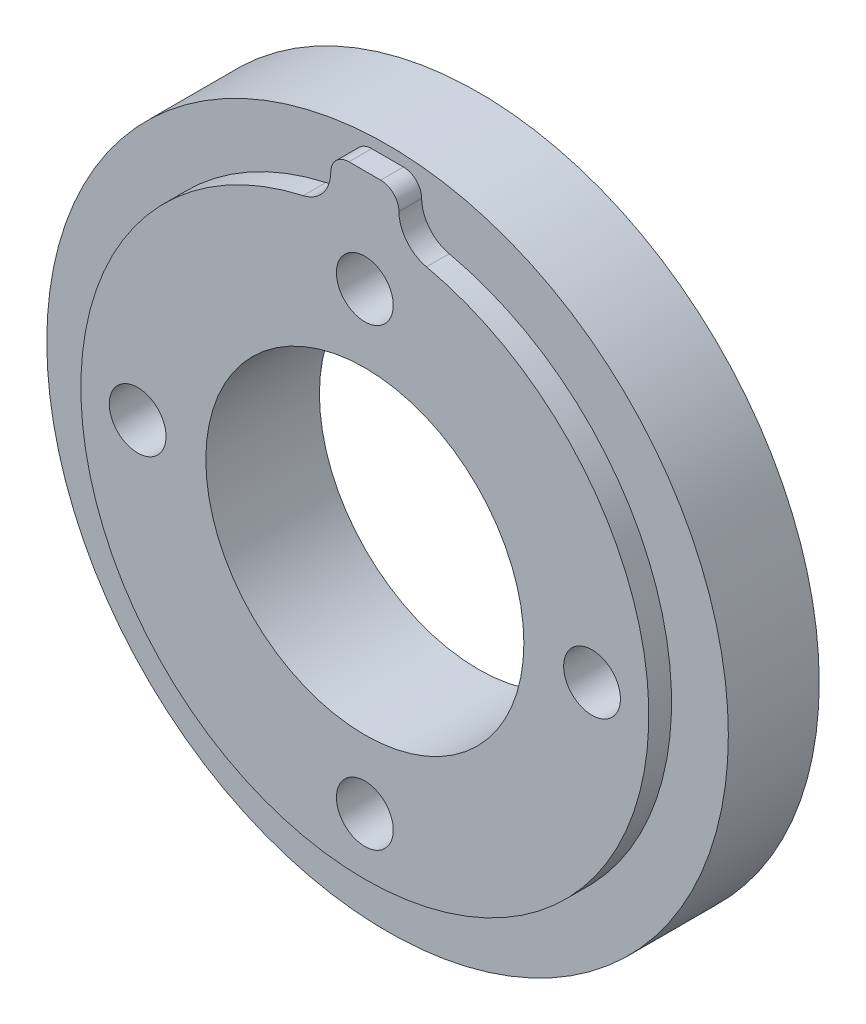
SolidWorks part; units mm, degrees
ref_plane "正面" through (0, 0, 0) normal (0, 0, 1) x (1, 0, 0)
ref_plane "平面" through (0, 0, 0) normal (0, 1, 0) x (1, 0, 0)
ref_plane "右側面" through (0, 0, 0) normal (1, 0, 0) x (0, 0, -1)
sketch "ｽｹｯﾁ1" plane through (0, 0, 0) normal (0, 0, 1) x (1, 0, 0)
  circle A0 centre (0, 0) radius 15
  dimension "D1" = 30
extrude "ﾎﾞｽ - 押し出し1" add sketch "ｽｹｯﾁ1" along normal blind 4
sketch "ｽｹｯﾁ2" plane through (0, 0, 4) normal (0, 0, 1) x (1, 0, 0)
  line L1 (-1.5, 10.5) -> (1.5, 10.5)
  line L2 (-1.5, 10.5) -> (-1.5, 14.5)
  line L3 (-1.5, 14.5) -> (1.5, 14.5)
  line L4 (1.5, 10.5) -> (1.5, 14.5)
  line L5 (-1.5, 10.5) -> (1.5, 14.5) construction
  line L6 (-1.5, 14.5) -> (1.5, 10.5) construction
  circle A0 centre (0, 0) radius 12.5
  point P3 (0, 12.5)
  circle M5 centre (0, 0) radius 15
  dimension "D1" = 25
  dimension "D2" = 2
  dimension "D3" = 3
extrude "ﾎﾞｽ - 押し出し2" add sketch "ｽｹｯﾁ2" along normal blind 1 contours A0 L4 L2 M5 | L4 L3 L2 M5 | L2 A0 L4 L1 | L4 A0 L2 L1 region at (0, 11.4852, 4) region at (0, -0.14, 4) region at (0, 13.4848, 4)
fillet "ﾌｨﾚｯﾄ1" radius 1.55 2 edges at (-1.5, 12.4097, 4.5) (1.5, 12.4097, 4.5)
fillet "ﾌｨﾚｯﾄ2" radius 0.8 2 edges at (1.5, 14.5, 4.5) (-1.5, 14.5, 4.5)
sketch "ｽｹｯﾁ3" plane through (0, 0, 5) normal (0, 0, 1) x (1, 0, 0)
  circle A0 centre (0, 0) radius 7
  dimension "D1" = 14
extrude "ｶｯﾄ - 押し出し1" cut sketch "ｽｹｯﾁ3" against normal through all
sketch "ｽｹｯﾁ4" plane through (0, 0, 0) normal (0, 0, -1) x (-1, 0, 0)
  circle A0 centre (0, 0) radius 10 construction
  circle A1 centre (0, 10) radius 1.25
  circle A2 centre (10, 0) radius 1.25
  circle A3 centre (0, -10) radius 1.25
  circle A4 centre (-10, 0) radius 1.25
  point P14 (0, 0)
  dimension "D1" = 20
  dimension "D2" = 2.5
  dimension "D3" = 4
extrude "ｶｯﾄ - 押し出し2" cut sketch "ｽｹｯﾁ4" against normal through all
